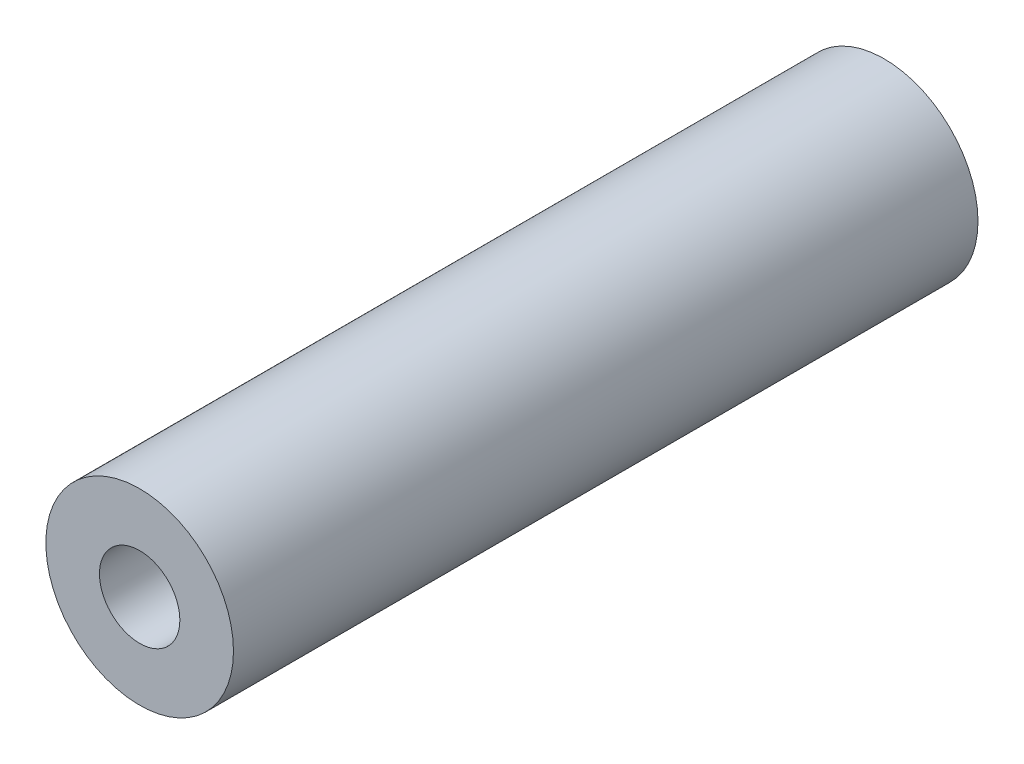
SolidWorks part; units mm, degrees
ref_plane "Front Plane" through (0, 0, 0) normal (0, 0, 1) x (1, 0, 0)
ref_plane "Top Plane" through (0, 0, 0) normal (0, 1, 0) x (1, 0, 0)
ref_plane "Right Plane" through (0, 0, 0) normal (1, 0, 0) x (0, 0, -1)
sketch "Sketch7" plane through (0, 0, 0) normal (0, 0, 1) x (1, 0, 0)
  circle A1 centre (-79.7199, 6.1443) radius 1.3716
  circle A2 centre (-79.7199, 6.1443) radius 3.2004
  dimension "D2" = 2.7432
  dimension "D1" = 6.4008
extrude "Boss-Extrude4" add sketch "Sketch7" along normal blind 25.4 separate body
ref_axis "Axis2" through (-79.7199, 6.1443, 32.3047) along (0, 0, -1)
equation "\"standoffHeight\"=\"1\""
equation "\"D1@Boss-Extrude4\" = \"standoffHeight\""
equation "\"screwDiameter\"=\"0.108\""
equation "\"D2@Sketch7\"=\"screwDiameter\""
